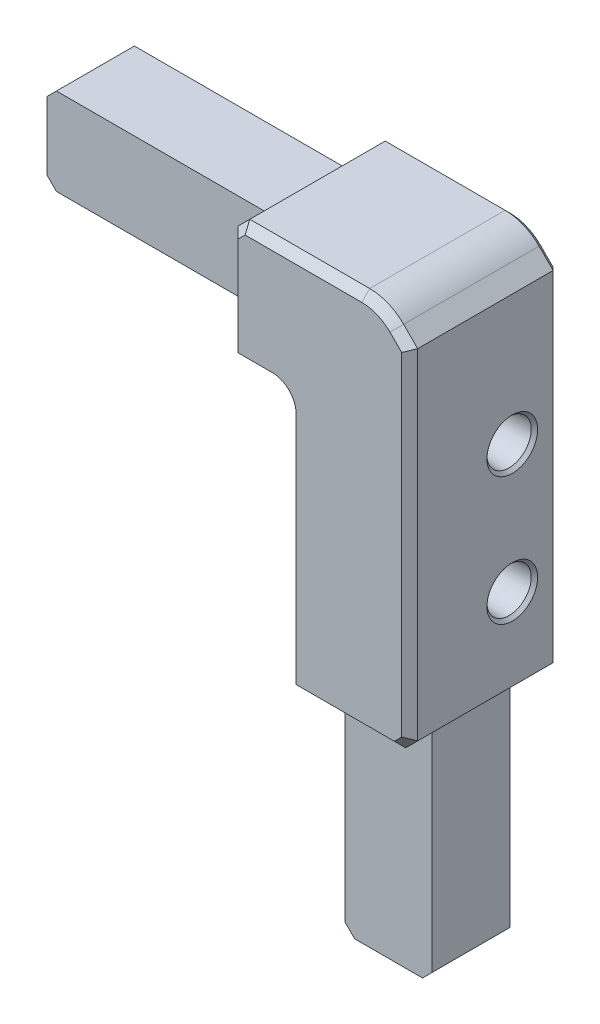
SolidWorks part; units mm, degrees
ref_plane "Front Plane" through (0, 0, 0) normal (0, 0, 1) x (1, 0, 0)
ref_plane "Top Plane" through (0, 0, 0) normal (0, 1, 0) x (1, 0, 0)
ref_plane "Right Plane" through (0, 0, 0) normal (1, 0, 0) x (0, 0, -1)
ref_plane "PZ 19.540" through (0, 0, 19.54) normal (0, 0, 1) x (1, 0, 0)
sketch "body sketch" plane through (0, 0, 19.54) normal (0, 0, 1) x (1, 0, 0)
  line L0 (4.42, 7.07) -> (-18.08, 7.07)
  line L1 (-18.08, 7.07) -> (-18.08, -8.13)
  line L2 (-18.08, -8.13) -> (-10.78, -8.13)
  line L3 (-10.78, -8.13) -> (-10.78, -40.43)
  line L4 (-10.78, -40.43) -> (4.42, -40.43)
  line L5 (4.42, -40.43) -> (4.42, 7.07)
extrude "body" add sketch "body sketch" along normal mid plane 11.42
ref_plane "PZ 20.375" through (0, 0, 20.375) normal (0, 0, 1) x (1, 0, 0)
sketch "side tongue sketch" plane through (0, 0, 20.375) normal (0, 0, 1) x (1, 0, 0)
  line L0 (-10.78, -70.43) -> (0.1, -70.43)
  line L1 (0.1, -70.43) -> (0.1, -39.43)
  line L2 (0.1, -39.43) -> (-10.78, -39.43)
  line L3 (-10.78, -39.43) -> (-10.78, -70.43)
extrude "side tongue" add sketch "side tongue sketch" along normal mid plane 9.75
sketch "end tongue sketch" plane through (0, 0, 20.375) normal (0, 0, 1) x (1, 0, 0)
  line L0 (-48.08, -8.13) -> (-17.08, -8.13)
  line L1 (-17.08, -8.13) -> (-17.08, 2.75)
  line L2 (-17.08, 2.75) -> (-48.08, 2.75)
  line L3 (-48.08, 2.75) -> (-48.08, -8.13)
extrude "end tongue" add sketch "end tongue sketch" along normal mid plane 9.75
ref_plane "PZ 23.100" through (0, 0, 23.1) normal (0, 0, 1) x (1, 0, 0)
sketch "web sketch" plane through (0, 0, 23.1) normal (0, 0, 1) x (1, 0, 0)
  line L0 (4.42, 7.07) -> (-18.08, 7.07)
  line L1 (-18.08, 7.07) -> (-18.08, 3)
  line L2 (-18.08, 3) -> (0.35, 3)
  line L3 (0.35, 3) -> (0.35, -40.43)
  line L4 (0.35, -40.43) -> (4.42, -40.43)
  line L5 (4.42, -40.43) -> (4.42, 7.07)
extrude "web" add sketch "web sketch" along normal mid plane 18.54
ref_plane "PZ 30.560" through (0, 0, 30.56) normal (0, 0, 1) x (1, 0, 0)
sketch "lip sketch" plane through (0, 0, 30.56) normal (0, 0, 1) x (1, 0, 0)
  line L0 (4.42, 7.07) -> (-18.08, 7.07)
  line L1 (-18.08, 7.07) -> (-18.08, -8.13)
  line L2 (-18.08, -8.13) -> (-10.78, -8.13)
  line L3 (-10.78, -8.13) -> (-10.78, -40.43)
  line L4 (-10.78, -40.43) -> (4.42, -40.43)
  line L5 (4.42, -40.43) -> (4.42, 7.07)
extrude "lip" add sketch "lip sketch" along normal mid plane 3.62
sketch "insert hole 1 sketch" plane through (0, 0, 19.54) normal (0, 0, 1) x (1, 0, 0)
  line L0 (-3.58, -28.7) -> (5.42, -28.7)
  line L1 (5.42, -28.7) -> (5.42, -24.5304)
  line L2 (5.42, -24.5304) -> (4.02, -25.9304)
  line L3 (4.02, -25.9304) -> (-1.98, -26.35)
  line L4 (-1.98, -26.35) -> (-3.58, -26.35)
  line L5 (-3.58, -26.35) -> (-3.58, -28.7)
revolve "insert hole 1" cut sketch "insert hole 1 sketch" angle 360 about L0
sketch "insert hole 2 sketch" plane through (0, 0, 19.54) normal (0, 0, 1) x (1, 0, 0)
  line L0 (-3.58, -12.7) -> (5.42, -12.7)
  line L1 (5.42, -12.7) -> (5.42, -8.5304)
  line L2 (5.42, -8.5304) -> (4.02, -9.9304)
  line L3 (4.02, -9.9304) -> (-1.98, -10.35)
  line L4 (-1.98, -10.35) -> (-3.58, -10.35)
  line L5 (-3.58, -10.35) -> (-3.58, -12.7)
revolve "insert hole 2" cut sketch "insert hole 2 sketch" angle 360 about L0
chamfer "bumper corner, bed side" distance 3.516 angle 45 1 edges at (4.42, 7.07, 23.1) tangent propagation no
fillet "bumper corner" radius 6 1 edges at (0.904, 7.07, 23.1) tangent propagation no
ref_plane "PZ 27.000" through (0, 0, 27) normal (0, 0, 1) x (1, 0, 0)
sketch "sheet corner relief sketch" plane through (0, 0, 27) normal (0, 0, 1) x (1, 0, 0)
  circle A0 centre (0.35, 3) radius 1
extrude "sheet corner relief" cut sketch "sheet corner relief sketch" against normal mid plane 3.5
fillet "reveal corner" radius 2 1 edges at (-10.78, -8.13, 30.56) tangent propagation no
fillet "body inside corner" radius 2 1 edges at (-10.78, -8.13, 19.54) tangent propagation no
chamfer "arm ends" distance 1.5 angle 45 2 edges at (-18.08, 7.07, 23.1) (4.42, -40.43, 23.1) tangent propagation no
chamfer "tongue lead-in" distance 1.2 angle 45 4 edges at (-48.08, -8.13, 20.375) (-48.08, 2.75, 20.375) (-10.78, -70.43, 20.375) (0.1, -70.43, 20.375) tangent propagation no
chamfer "front face chamfer" distance 1 angle 45 11 edges at (0.7148, 6.6133, 32.37) (3.5407, 4.4333, 32.37) (4.42, -17.688, 32.37) (3.67, -39.68, 32.37) (-3.93, -40.43, 32.37) (-10.78, -25.28, 32.37) (-11.3658, -8.7158, 32.37) (-15.43, -8.13, 32.37) (-18.08, -1.28, 32.37) (-17.33, 6.32, 32.37) (-9.0806, 7.07, 32.37)
chamfer "back face chamfer" distance 0.6 angle 45 11 edges at (-15.43, -8.13, 13.83) (-11.3658, -8.7158, 13.83) (-10.78, -25.28, 13.83) (-3.93, -40.43, 13.83) (3.67, -39.68, 13.83) (4.42, -17.688, 13.83) (3.5407, 4.4333, 13.83) (0.7148, 6.6133, 13.83) (-9.0806, 7.07, 13.83) (-17.33, 6.32, 13.83) (-18.08, -1.28, 13.83)
equation "\"diffL\"= 608.8mm"
equation "\"diffW\"= 329.4mm"
equation "\"diffT\"= 2.9mm"
equation "\"chanSlotW\"= 12.9mm"
equation "\"chanSlotDepth\"= 11.13mm"
equation "\"chanFloor\"= 1.57mm"
equation "\"chanLeg\"= 12.7mm"
equation "\"lightL\"= 605mm"
equation "\"lightW\"= 331mm"
equation "\"lightH\"= 92mm"
equation "\"lightSideFlat\"= 30mm"
equation "\"lightSlopeLen\"= 33.1mm"
equation "\"lightWingDepth\"= 47.9mm"
equation "\"lightWingFlat\"= 90.2mm"
equation "\"lightChanW\"= 99.6mm"
equation "\"lightChanStand\"= 44.1mm"
equation "\"insFlangeD\"= 12.3mm"
equation "\"insFromEnd\"= 20.7mm"
equation "\"insUpSlope\"= 20.8mm"
equation "\"gaugeH\"= 10mm"
equation "\"gaugeStepLen\"= 14mm"
equation "\"gaugeStepW0\"= 13.1mm"
equation "\"gaugeStepDW\"= 0.2mm"
equation "\"gaugeSteps\"= 5mm"
equation "\"gaugeHandleLen\"= 30mm"
equation "\"gaugeHandleW\"= 24mm"
equation "\"gaugeSlot0\"= 3mm"
equation "\"gaugeSlotD\"= 0.1mm"
equation "\"gaugeSlotDepth\"= 8mm"
equation "\"gap\"= 25.4mm"
equation "\"edgeL\"= 1mm"
equation "\"edgeW\"= 0.75mm"
equation "\"proud\"= 1.5mm"
equation "\"seatClr\"= 0.15mm"
equation "\"tongueClrZ\"= 0.1mm"
equation "\"tongueClrX\"= 0.25mm"
equation "\"tongueLen\"= 30mm"
equation "\"armSide\"= 45mm"
equation "\"armEnd\"= 20mm"
equation "\"cornerCham\"= 3mm"
equation "\"brkW\"= 26mm"
equation "\"brkT\"= 7mm"
equation "\"brkSeatClr\"= 0.2mm"
equation "\"brkScrewSpan\"= 16mm"
equation "\"pilotD\"= 2.7mm"
equation "\"pilotDepth\"= 10mm"
equation "\"screwClrD\"= 3.9mm"
equation "\"jogBelow\"= 4mm"
equation "\"padT\"= 7mm"
equation "\"padLen\"= 31mm"
equation "\"m6Clr\"= 7mm"
equation "\"m6Slot\"= 3mm"
equation "\"flangeRelD\"= 17mm"
equation "\"flangeRelDepth\"= 1.5mm"
equation "\"relLen\"= 7mm"
equation "\"relDepth\"= 4mm"
equation "\"relLand\"= 2mm"
equation "\"knockN\"= 100mm"
equation "\"petgcfE\"= 3000mm"
equation "\"mockExtent\"= 110mm"
equation "\"relZnear\"= 9.4mm"
equation "\"relZfar\"= 23.4mm"
equation "\"headD\"= 8mm"
equation "\"headH\"= 2.5mm"
equation "\"headFromEnd\"= 6.8mm"
equation "\"headBack\"= 16.4mm"
equation "\"sideClr\"= 0.4mm"
equation "\"cornerRelR\"= 1.5mm"
equation "\"cornerRelBack\"= 0.6mm"
equation "\"endHeadH\"= 2.8mm"
equation "\"footClr\"= 1.2mm"
equation "\"footEndClr\"= 3.5mm"
equation "\"footLift\"= 6mm"
equation "\"footBlockClr\"= 0.5mm"
equation "\"footBack\"= 50mm"
equation "\"footFwd\"= 10mm"
equation "\"footBraceEnd\"= 3mm"
equation "\"footLoadN\"= 25mm"
equation "\"spacerLen\"= 60mm"
equation "\"spacerShort\"= 0.5mm"
equation "\"spacerCham\"= 0.8mm"
equation "\"spacerPerSide\"= 3mm"
equation "\"spacerPerEnd\"= 1mm"
equation "\"toolR\"= 9mm"
equation "\"visR\"= 4mm"
equation "\"edgeR\"= 1mm"
equation "\"bendOutR\"= 5mm"
equation "\"insideR\"= 2.5mm"
equation "\"footCornerR\"= 10mm"
equation "\"footFrontR\"= 8mm"
equation "\"braceKinkR\"= 12mm"
equation "\"bedCham\"= 1mm"
equation "\"bedChamSmall\"= 0.6mm"
equation "\"soleTopR\"= 2mm"
equation "\"cornerR\"= 6mm"
equation "\"rimInR\"= 1mm"
equation "\"insFlangeH\"= 1mm"
equation "\"insHoleFinishD\"= 4.5mm"
equation "\"insLen\"= 6.4mm"
equation "\"footToeTip\"= 4mm"
equation "\"cgInset\"= 4mm"
equation "\"lampWeightN\"= 51mm"
equation "\"frameWeightN\"= 10mm"
equation "\"bumpIn\"= 8mm"
equation "\"bumpH\"= 3mm"
equation "\"legBelowFront\"= 2mm"
equation "\"lipClr\"= 0.1mm"
equation "\"revealR\"= 2mm"
equation "\"frontCham\"= 1mm"
equation "\"insHoleBotD\"= 4.7mm"
equation "\"insTaperDeg\"= 8mm"
equation "\"insMouthCham\"= 0.4mm"
equation "\"leanDeg\"= 5mm"
equation "\"footTailT\"= 6mm"
equation "\"v1LeanDeg\"= 4.5mm"
equation "\"toeNoseR\"= 5mm"
equation "\"petgE\"= 2000mm"
equation "\"cheekT\"= 8mm"
equation "\"handleUp\"= 50mm"
equation "\"handleZ\"= -10mm"
equation "\"gripD\"= 19.05mm"
equation "\"gripClr\"= 0.5mm"
equation "\"bossWall\"= 5mm"
equation "\"bossLen\"= 14mm"
equation "\"socketFloor\"= 4mm"
equation "\"barEndClr\"= 1mm"
equation "\"lipH\"= 4mm"
equation "\"lipDeep\"= 6mm"
equation "\"stripT\"= 1.3mm"
equation "\"stripW\"= 12mm"
equation "\"stripClr\"= 0.5mm"
equation "\"stripBack\"= 3mm"
equation "\"endRelClr\"= 1mm"
equation "\"cornerScrewX\"= 5.5mm"
equation "\"cornerScrewZ\"= 6mm"
equation "\"cornerScrewD\"= 8.5mm"
equation "\"footTabIn\"= 33mm"
equation "\"footTabZ1\"= 50mm"
equation "\"footTabZ2\"= 19mm"
equation "\"footTabR\"= 8mm"
equation "\"landAx0\"= -17mm"
equation "\"landAz0\"= -30mm"
equation "\"landAx1\"= -3mm"
equation "\"landAz1\"= -18mm"
equation "\"landBx0\"= -60mm"
equation "\"landBz0\"= -43mm"
equation "\"landBx1\"= -46mm"
equation "\"landBz1\"= -27mm"
equation "\"sdLidW\"= 84.15mm"
equation "\"sdChanW\"= 80.19mm"
equation "\"sdLidStep\"= 1.7mm"
equation "\"sdInsRecess\"= 0.81mm"
equation "\"sdInsSpan\"= 59.21mm"
equation "\"sdJunkIn\"= 10.36mm"
equation "\"sdJunkH\"= 4.32mm"
equation "\"sdJunkLen\"= 110mm"
equation "\"sdHandleY\"= 0mm"
equation "\"sdInsDown\"= 21.3mm"
equation "\"sdSkirtH\"= 10.5mm"
equation "\"sdWallDown\"= 37mm"
equation "\"sdLidClr\"= 0.8mm"
equation "\"sdWasherT\"= 1.6mm"
equation "\"sdWasherD\"= 12mm"
equation "\"sdLegT\"= 5mm"
equation "\"sdLegBelow\"= 11mm"
equation "\"sdLegHalf\"= 46mm"
equation "\"sdSkirtSlope\"= 50mm"
equation "\"sdLipH\"= 5mm"
equation "\"sdLeadCham\"= 1mm"
equation "\"sdJunkSide\"= 1.5mm"
equation "\"sdRecessH\"= 6mm"
equation "\"sdRoofT\"= 6mm"
equation "\"sdOpenL\"= 114.3mm"
equation "\"sdOpenH\"= 44.45mm"
equation "\"sdGripD\"= 25mm"
equation "\"sdBendR\"= 18mm"
equation "\"sdBaseR\"= 8mm"
equation "\"sdEndMargin\"= 2mm"
equation "\"sdSlotW\"= 8mm"
equation "\"sdSlotFloat\"= 1mm"
equation "\"sdEdgeR\"= 2mm"
equation "\"sheetReliefR\"= 1mm"
